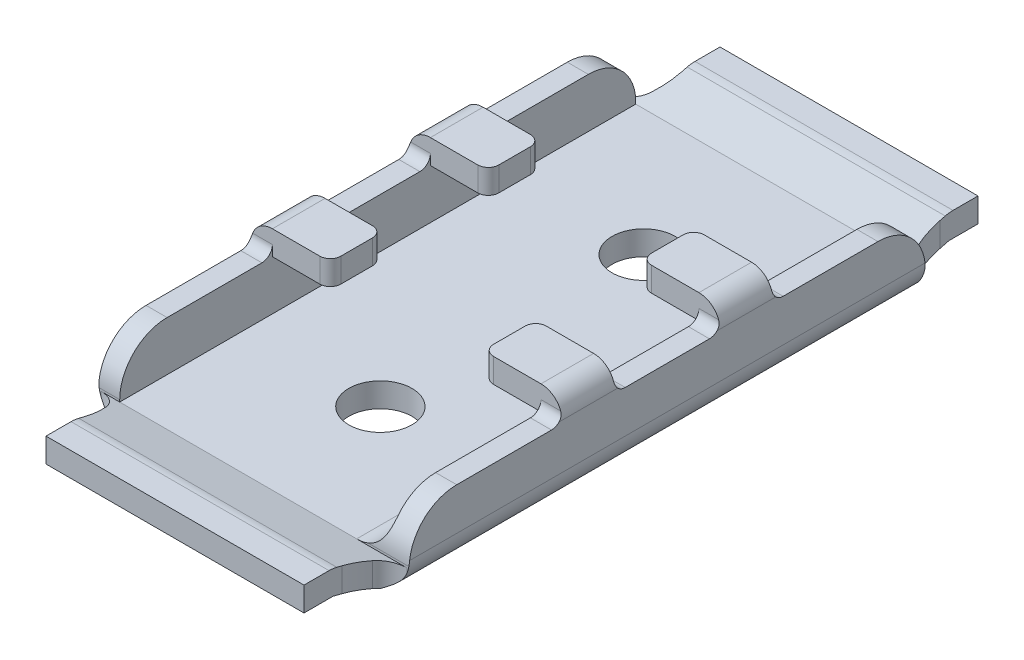
SolidWorks part; units mm, degrees
ref_plane "Plano frontal" through (0, 0, 0) normal (0, 0, 1) x (1, 0, 0)
ref_plane "Plano superior" through (0, 0, 0) normal (0, 1, 0) x (1, 0, 0)
ref_plane "Plano direito" through (0, 0, 0) normal (1, 0, 0) x (0, 0, -1)
sketch "Esboço1" plane through (0, 0, 0) normal (1, 0, 0) x (0, 0, -1)
  line L0 (-32, 8.6751) -> (-32, 6.3751)
  line L1 (-32, 6.3751) -> (-29.25, 6.3751)
  line L2 (-29.25, 6.3751) -> (-24.5, 5.1751)
  line L3 (0, 0) -> (0, 30.8029) construction
  line L4 (-24.5, 5.1751) -> (24.5, 5.1751)
  line L5 (-32, 8.6751) -> (-29.25, 8.6751)
  line L6 (-29.25, 8.6751) -> (-24.5, 7.4751)
  line L7 (-24.5, 7.4751) -> (24.5, 7.4751)
  line L8 (29.25, 8.6751) -> (24.5, 7.4751)
  line L9 (32, 8.6751) -> (29.25, 8.6751)
  line L10 (29.25, 6.3751) -> (24.5, 5.1751)
  line L11 (32, 6.3751) -> (29.25, 6.3751)
  line L12 (32, 8.6751) -> (32, 6.3751)
  point P12 (0, 7.4751)
  point P15 (0, 5.1751)
  dimension "D1" = 64
  dimension "D2" = 2.75
  dimension "D3" = 2.75
  dimension "D4" = 2.3
  dimension "D5" = 7.5
  dimension "D6" = 7.5
  dimension "D7" = 1.2
extrude "Ressalto-extrusão1" add sketch "Esboço1" along normal blind 29.5
sketch "Esboço2" plane through (0, 5.1751, 0) normal (0, -1, 0) x (1, 0, 0)
  line L0 (14.75, 24.5) -> (14.75, 32) construction
  line L1 (29.5, 24.5) -> (0, 24.5) construction
  line L2 (29.5, 32) -> (0, 32) construction
  line L3 (2.5, 32) -> (27, 32)
  line L4 (2.5, 32) -> (2.5, 25.5)
  line L5 (2.5, 25.5) -> (0, 23)
  line L6 (2.5, 32) -> (2.5, 25.5)
  line L7 (0, 0) -> (31.6455, 0) construction
  line L8 (27, 25.5) -> (29.5, 23)
  line L9 (27, 32) -> (27, 25.5)
  line L10 (2.5, 25.5) -> (0, 23)
  line L11 (27, 25.5) -> (29.5, 23)
  line L12 (27, 32) -> (27, 25.5)
  line L13 (2.5, 32) -> (2.5, 25.5)
  line L14 (2.5, 25.5) -> (0, 23)
  line L15 (27, 25.5) -> (29.5, 23)
  line L16 (2.5, 32) -> (2.5, 25.5)
  line L17 (2.5, 25.5) -> (0, 23)
  line L18 (27, 32) -> (27, 25.5)
  line L19 (27, 25.5) -> (29.5, 23)
  line L20 (27, 32) -> (27, 25.5)
  line L21 (2.5, -25.5) -> (0, -23)
  line L22 (27, -25.5) -> (29.5, -23)
  line L23 (27, -32) -> (27, -25.5)
  line L24 (2.5, -32) -> (2.5, -25.5)
  line L25 (2.5, -32) -> (27, -32)
  line L26 (0, 23) -> (-20.6574, 23)
  line L27 (-20.6574, 23) -> (-20.6574, 38.284)
  line L28 (-20.6574, 38.284) -> (40.7731, 38.284)
  line L29 (40.7731, 38.284) -> (40.7731, 23)
  line L30 (40.7731, 23) -> (29.5, 23)
  line L31 (0, -23) -> (-11.6157, -23)
  line L32 (-11.6157, -23) -> (-11.6157, -35.4681)
  line L33 (-11.6157, -35.4681) -> (39.2661, -35.4681)
  line L34 (39.2661, -35.4681) -> (39.2661, -23)
  line L35 (39.2661, -23) -> (29.5, -23)
  line M1 (0, 24.5) -> (0, -24.5)
  line M2 (0, -24.5) -> (29.5, -24.5)
  line M3 (29.5, -24.5) -> (29.5, 24.5)
  line M4 (29.5, 24.5) -> (0, 24.5)
  dimension "D1" = 24.5
  dimension "D2" = 6.5
  dimension "D3" = 9
extrude "Corte-extrusão1" cut sketch "Esboço2" against normal through all contours L30 L29 L28 L27 L26 L5 L4 L3 L9 L8 M1 M4 M3 | L34 L35 L22 L23 L25 L24 L21 L31 L32 L33 M3 M2 M1
sketch "Esboço3" plane through (0, 7.4751, 0) normal (0, 1, 0) x (1, 0, 0)
  line L0 (28, -24.5) -> (1.5, -24.5) construction
  line L1 (0, 24.5) -> (2, 24.5)
  line L2 (0, 24.5) -> (0, -24.5)
  line L3 (0, -24.5) -> (2, -24.5)
  line L4 (2, 24.5) -> (2, -24.5)
  line L5 (14.75, 24.5) -> (14.75, 5.8389) construction
  line L6 (28, 24.5) -> (1.5, 24.5) construction
  line L7 (29.5, -24.5) -> (27.5, -24.5)
  line L8 (29.5, 24.5) -> (27.5, 24.5)
  line L9 (27.5, 24.5) -> (27.5, -24.5)
  line L10 (29.5, 24.5) -> (29.5, -24.5)
  dimension "D1" = 2
extrude "Ressalto-extrusão2" add sketch "Esboço3" along normal blind 4.7
sketch "Esboço4" plane through (0, 12.1751, 0) normal (0, 1, 0) x (1, 0, 0)
  line L0 (0, 0) -> (-6.2865, 0) construction
  line L1 (0, 24.5) -> (0, -24.5) construction
  line L2 (0, 7.5) -> (0, -7.5) construction
  line L3 (0, 10) -> (0, 5)
  line L4 (0, 10) -> (7.5, 10)
  line L5 (7.5, 10) -> (7.5, 5)
  line L6 (7.5, 5) -> (0, 5)
  line L7 (7.5, -5) -> (0, -5)
  line L8 (7.5, -10) -> (7.5, -5)
  line L9 (0, -10) -> (7.5, -10)
  line L10 (0, -10) -> (0, -5)
  line L11 (14.75, 24.5) -> (14.75, 17.4338) construction
  line L12 (27.5, 24.5) -> (2, 24.5) construction
  line L13 (29.5, -10) -> (29.5, -5)
  line L14 (29.5, -10) -> (22, -10)
  line L15 (22, -10) -> (22, -5)
  line L16 (22, -5) -> (29.5, -5)
  line L17 (22, 5) -> (29.5, 5)
  line L18 (22, 10) -> (22, 5)
  line L19 (29.5, 10) -> (22, 10)
  line L20 (29.5, 10) -> (29.5, 5)
extrude "Ressalto-extrusão3" add sketch "Esboço4" along normal blind 2.3
fillet "Filete1" radius 2 4 edges at (0, 14.4751, 7.5) (0, 14.4751, -7.5) (29.5, 14.4751, -7.5) (29.5, 14.4751, 7.5)
fillet "Filete2" radius 1 8 edges at (22, 13.3251, -5) (22, 13.3251, -10) (7.5, 13.3251, -10) (7.5, 13.3251, -5) (7.5, 13.3251, 10) (22, 13.3251, 10) (22, 13.3251, 5) (7.5, 13.3251, 5)
fillet "Filete4" radius 4.5 4 edges at (28.5, 12.1751, 24.5) (28.5, 12.1751, -24.5) (1, 12.1751, -24.5) (1, 12.1751, 24.5)
fillet "Filete5" radius 1 6 edges at (28.5, 12.1751, -5) (1, 12.1751, 10)
fillet "Filete6" radius 1 1 edges at (28.5, 12.1751, -10)
fillet "Filete11" radius 8 1 edges at (27, 6.5777, -25.5)
fillet "Filete12" radius 8 1 edges at (2.5, 6.5777, -25.5)
fillet "Filete13" radius 8 1 edges at (2.5, 6.5777, 25.5)
fillet "Filete14" radius 8 1 edges at (27, 6.5777, 25.5)
fillet "Filete19" radius 3 2 edges at (14.75, 8.6751, 29.25) (14.75, 8.6751, -29.25)
sketch "Esboço5" plane through (0, 5.1751, 0) normal (0, -1, 0) x (1, 0, 0)
  line L0 (0, 0) -> (29.5, 0) construction
  line L1 (29.5, 24.5) -> (29.5, -24.5) construction
  line L2 (14.75, 12.5) -> (14.75, -12.5) construction
  circle A0 centre (14.75, 12.5) radius 3
  circle A1 centre (14.75, -12.5) radius 3
  dimension "D1" = 6
  dimension "D2" = 6
extrude "Corte-extrusão2" cut sketch "Esboço5" against normal through all
fillet "Filete20" radius 2 1 edges at (1.5, 6.3251, 24.5)
fillet "Filete21" radius 2 1 edges at (28, 6.3251, 24.5)
fillet "Filete22" radius 2 1 edges at (28, 6.3251, -24.5)
fillet "Filete23" radius 2 1 edges at (1.5, 6.3251, -24.5)
fillet "Filete25" radius 3 2 edges at (0, 5.1751, 0) (27.5, 7.4751, 0)
fillet "Filete26" radius 3 1 edges at (29.5, 5.1751, 0)
